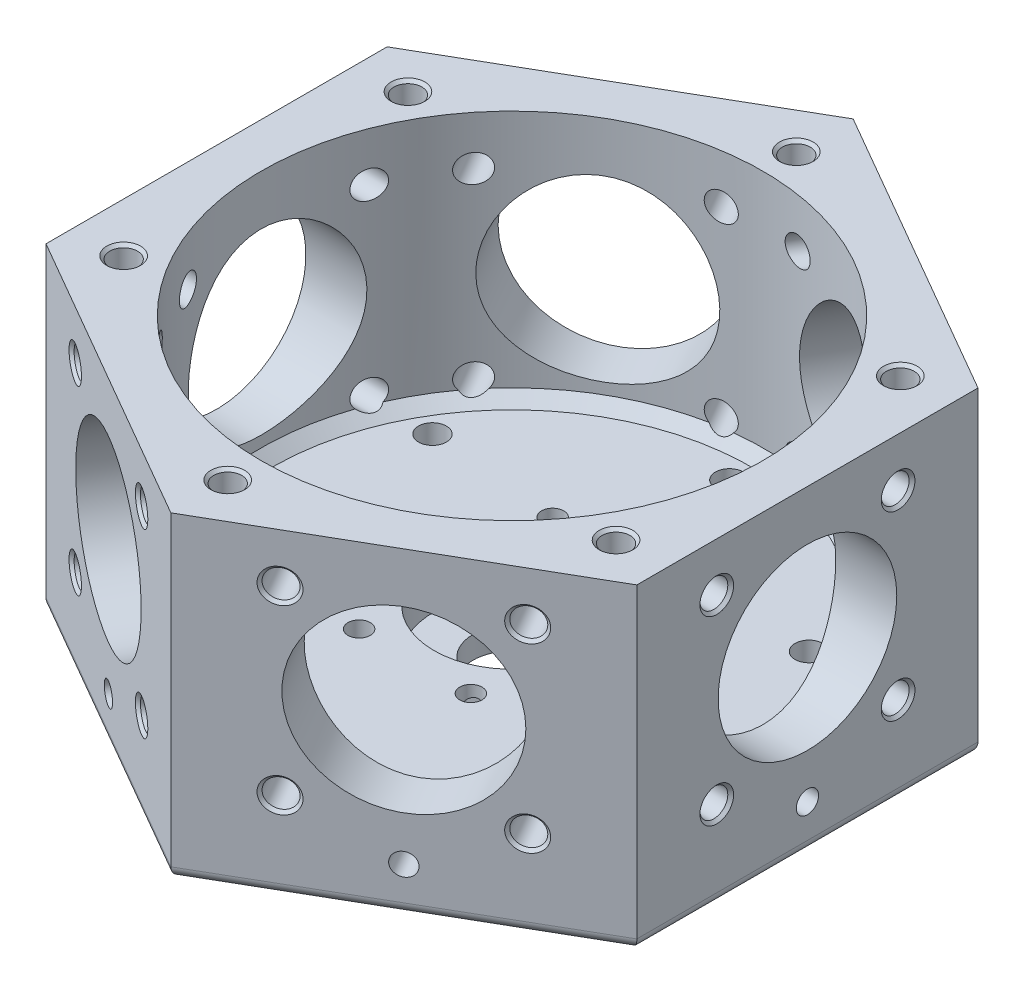
SolidWorks part; units mm, degrees
material "1023 Carbon Steel Sheet (SS)"
ref_plane "Front Plane" through (0, 0, 0) normal (0, 0, 1) x (1, 0, 0)
ref_plane "Top Plane" through (0, 0, 0) normal (0, 1, 0) x (1, 0, 0)
ref_plane "Right Plane" through (0, 0, 0) normal (1, 0, 0) x (0, 0, -1)
sketch "Sketch1" plane through (0, 0, 0) normal (0, 1, 0) x (1, 0, 0)
  line L1 (0, -61.1991) -> (53, -30.5996)
  line L2 (53, -30.5996) -> (53, 30.5996)
  line L3 (53, 30.5996) -> (0, 61.1991)
  line L4 (0, 61.1991) -> (-53, 30.5996)
  line L5 (-53, 30.5996) -> (-53, -30.5996)
  line L6 (-53, -30.5996) -> (0, -61.1991)
  circle A0 centre (0, 0) radius 53 construction
  dimension "D1" = 106
extrude "Boss-Extrude1" add sketch "Sketch1" along normal blind 25 and the other way blind 32
sketch "Sketch2" plane through (0, 25, 0) normal (0, 1, 0) x (1, 0, 0)
  circle A0 centre (0, 0) radius 45
  dimension "D1" = 90
extrude "Cut-Extrude1" cut sketch "Sketch2" against normal blind 45 contours A0
sketch "Sketch5" plane through (-26.5, 0, 45.8993) normal (-0.5, 0, 0.866) x (0.866, 0, 0.5)
  circle A0 centre (0, 0) radius 16.025
  dimension "D1" = 32.05
extrude "Cut-Extrude2" cut sketch "Sketch5" against normal up to next contours A0
pattern_circular "CirPattern1" count 6 over 360 about axis through (0, 25, 0) along (0, 1, 0) of "Cut-Extrude2"
chamfer "Chamfer1" distance 2 angle 45 1 edges at (0, -20, 45)
fillet "Fillet1" radius 2 6 edges at (26.5, -32, 45.8993) (53, -32, 0) (26.5, -32, -45.8993) (-26.5, -32, -45.8993) (-53, -32, 0) (-26.5, -32, 45.8993)
sketch "Sketch6" plane through (0, 25, 0) normal (0, 1, 0) x (1, 0, 0)
  line L0 (0, 0) -> (0, 51) construction
  circle A0 centre (0, 0) radius 51 construction
  dimension "D1" = 102
hole_wizard "M6 Tapped Hole1" positions "3DSketch1" profile "Sketch7" tap size "M6" standard "ISO"
sketch3d "3DSketch1"
  point P0 (0, 25, -51)
sketch "Sketch7" plane through (0, 25, -51) normal (1, 0, 0) x (0, 0, 1)
  line L0 (0, 0) -> (0, 13.5022)
  line L1 (0, 13.5022) -> (2.5, 12)
  line L2 (2.5, 12) -> (2.5, 0.525)
  line L3 (2.5, 0.525) -> (3.025, 0)
  line L5 (3.025, 0) -> (0, 0)
  line L6 (-2.5, 0.525) -> (-3.025, 0) construction
  line L10 (0, 13.5022) -> (-2.5, 12) construction
  line L11 (0, -6.35) -> (0, 107.95) construction
  dimension "Tap Drill Dia." = 5
  dimension "Tap Drill Depth" = 12
  dimension "Near C'Sink Dia." = 6.05
  dimension "Near C'Sink Angle" = 90
  dimension "Drill Angle" = 118
pattern_circular "CirPattern2" count 6 over 360 about axis through (0, 0, 0) along (0, 1, 0) of "M6 Tapped Hole1"
sketch "Sketch8" plane through (26.5, 0, 45.8993) normal (0.5, 0, 0.866) x (0.866, 0, -0.5)
  line L0 (23, 0) -> (0, 0) construction
  line L1 (0, 0) -> (16.2635, 16.2635) construction
  circle A0 centre (0, 0) radius 23
  dimension "D1" = 46
  dimension "D2" = 45
hole_wizard "M6 Tapped Hole2" positions "3DSketch2" profile "Sketch9" tap size "M6" standard "ISO"
sketch3d "3DSketch2"
  point P0 (40.5846, 16.2635, 37.7676)
sketch "Sketch9" plane through (40.5846, 16.2635, 37.7676) normal (0, 1, 0) x (0.866, 0, -0.5)
  line L0 (0, 0) -> (0, 16.5022)
  line L1 (0, 16.5022) -> (2.5, 15)
  line L2 (2.5, 15) -> (2.5, 0.525)
  line L3 (2.5, 0.525) -> (3.025, 0)
  line L5 (3.025, 0) -> (0, 0)
  line L6 (-2.5, 0.525) -> (-3.025, 0) construction
  line L10 (0, 16.5022) -> (-2.5, 15) construction
  line L11 (0, -6.35) -> (0, 107.95) construction
  dimension "Tap Drill Dia." = 5
  dimension "Tap Drill Depth" = 15
  dimension "Near C'Sink Dia." = 6.05
  dimension "Near C'Sink Angle" = 90
  dimension "Drill Angle" = 118
pattern_circular "CirPattern3" count 4 over 360 about axis through (0, 0, 0) along (0.5, 0, 0.866) of "M6 Tapped Hole2"
pattern_circular "CirPattern4" count 6 over 360 about axis through (0, 25, 0) along (0, 1, 0) of "CirPattern3", "M6 Tapped Hole2"
sketch "Sketch10" plane through (0, -32, 0) normal (0, -1, 0) x (1, 0, 0)
  line L0 (0, 0) -> (0, 39) construction
  circle A0 centre (0, 0) radius 39 construction
  dimension "D1" = 78
hole_wizard "M6 Tapped Hole3" positions "3DSketch3" profile "Sketch11" tap size "M6" standard "ISO"
sketch3d "3DSketch3"
  point P0 (0, -32, 39)
sketch "Sketch11" plane through (0, -32, 39) normal (1, 0, 0) x (0, 0, -1)
  line L0 (0, 0) -> (0, 16.5022)
  line L1 (0, 16.5022) -> (2.5, 15)
  line L2 (2.5, 15) -> (2.5, 0.525)
  line L3 (2.5, 0.525) -> (3.025, 0)
  line L5 (3.025, 0) -> (0, 0)
  line L6 (-2.5, 0.525) -> (-3.025, 0) construction
  line L10 (0, 16.5022) -> (-2.5, 15) construction
  line L11 (0, -6.35) -> (0, 107.95) construction
  dimension "Tap Drill Dia." = 5
  dimension "Tap Drill Depth" = 15
  dimension "Near C'Sink Dia." = 6.05
  dimension "Near C'Sink Angle" = 90
  dimension "Drill Angle" = 118
pattern_circular "CirPattern5" count 6 over 360 about axis through (0, 0, 0) along (0, 1, 0) of "M6 Tapped Hole3"
sketch "Sketch12" plane through (0, -32, 0) normal (0, -1, 0) x (1, 0, 0)
  circle A0 centre (0, 0) radius 20 construction
  circle A1 centre (20, 0) radius 2
  dimension "D1" = 40
  dimension "D2" = 4
extrude "Cut-Extrude3" cut sketch "Sketch12" against normal through all contours A1
pattern_circular "CirPattern6" count 6 over 360 about axis through (-0.0443, 0, 0) along (0, 1, 0) of "Cut-Extrude3"
sketch "Sketch13" plane through (53, 0, 0) normal (1, 0, 0) x (0, 0, -1)
  circle A0 centre (0, -24) radius 2
  dimension "D1" = 4
  dimension "D2" = 24
extrude "Cut-Extrude4" cut sketch "Sketch13" against normal blind 36
pattern_circular "CirPattern7" count 6 over 360 about axis through (0, 0, 0) along (0, 1, 0) of "Cut-Extrude4"
sketch "Sketch14" plane through (0, -32, 0) normal (0, -1, 0) x (1, 0, 0)
  circle A0 centre (0, 0) radius 7
  dimension "D1" = 14
extrude "Cut-Extrude5" cut sketch "Sketch14" against normal through all
sketch "Sketch15" plane through (0, -20, 0) normal (0, 1, 0) x (1, 0, 0)
  circle A0 centre (0, 0) radius 14
  dimension "D1" = 28
extrude "Cut-Extrude6" cut sketch "Sketch15" against normal blind 8
